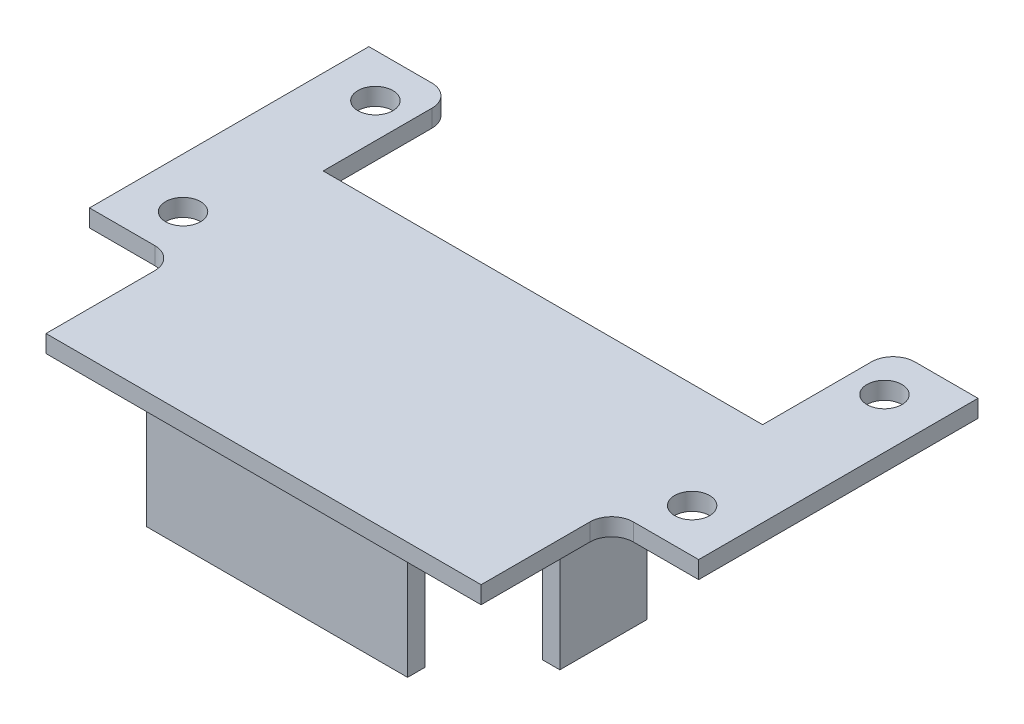
SolidWorks part; units mm, degrees
ref_plane "Front Plane" through (0, 0, 0) normal (0, 0, 1) x (1, 0, 0)
ref_plane "Top Plane" through (0, 0, 0) normal (0, 1, 0) x (1, 0, 0)
ref_plane "Right Plane" through (0, 0, 0) normal (1, 0, 0) x (0, 0, -1)
sketch "Sketch1" plane through (0, 0, 0) normal (0, 1, 0) x (1, 0, 0)
  line L0 (0, 0) -> (0, 20.3835) construction
  line L1 (44.45, -20.3835) -> (-44.45, -20.3835)
  line L2 (44.45, -20.3835) -> (44.45, 20.3835)
  line L3 (44.45, 20.3835) -> (-44.45, 20.3835) construction
  line L4 (-44.45, -20.3835) -> (-44.45, 20.3835)
  line L5 (44.45, -20.3835) -> (-44.45, 20.3835) construction
  line L6 (44.45, 20.3835) -> (-44.45, -20.3835) construction
  line L7 (0, 0) -> (44.45, 0) construction
  line L13 (-32.0675, 17.2085) -> (-32.0675, 1.3335)
  line L14 (-44.45, 20.3835) -> (-35.2425, 20.3835)
  line L15 (-32.0675, 1.3335) -> (32.0675, 1.3335)
  line L16 (32.0675, 17.2085) -> (32.0675, 1.3335)
  line L17 (44.45, 20.3835) -> (35.2425, 20.3835)
  circle A0 centre (37.1475, -14.0335) radius 2.5527
  circle A2 centre (37.1475, 14.0335) radius 2.5527
  circle A3 centre (-37.1475, -14.0335) radius 2.5527
  circle A4 centre (-37.1475, 14.0335) radius 2.5527
  arc A7 (-32.0675, 17.2085) -> (-35.2425, 20.3835) centre (-35.2425, 17.2085) ccw
  arc A8 (32.0675, 17.2085) -> (35.2425, 20.3835) centre (35.2425, 17.2085) cw
  point P0 (0, 0)
  point P19 (0, 1.3335)
  point P22 (0, 20.3835)
  point P23 (-32.0675, 20.3835)
  point P24 (44.45, 0)
  point P30 (32.0675, 20.3835)
  dimension "D3" = 5.1054
  dimension "D6" = 28.067
  dimension "D7" = 5.1054
  dimension "D10" = 5.08
  dimension "D12" = 3.175
  dimension "D1" = 6.35
  dimension "D2" = 88.9
  dimension "D4" = 6.35
  dimension "D5" = 7.3025
  dimension "D8" = 7.3025
  dimension "D11" = 19.05
extrude "Boss-Extrude1" add sketch "Sketch1" along normal blind 2.54
sketch "Sketch7" plane through (0, 2.54, 0) normal (0, 1, 0) x (1, 0, 0)
  line L1 (-44.45, -20.3835) -> (44.45, -20.3835)
  line L2 (-44.45, -20.3835) -> (-44.45, -39.4335)
  line L3 (-44.45, -39.4335) -> (44.45, -39.4335)
  line L4 (44.45, -20.3835) -> (44.45, -39.4335)
  dimension "D1" = 19.05
extrude "Boss-Extrude2" add sketch "Sketch7" against normal up to surface (2.54 mm away) up to face at (0, 0, -7.9166)
sketch "Sketch6" plane through (0, 0, 0) normal (0, -1, 0) x (-1, 0, 0)
  line L0 (0, 1.3335) -> (0, -39.4335) construction
  line L5 (-32.0675, 1.3335) -> (32.0675, 1.3335) construction
  line L11 (-44.45, -39.4335) -> (44.45, -39.4335) construction
  line L26 (25.4, -33.655) -> (-25.4, -33.655) construction
  line L27 (25.4, -33.655) -> (25.4, -4.445) construction
  line L28 (25.4, -4.445) -> (-25.4, -4.445) construction
  line L29 (-25.4, -33.655) -> (-25.4, -4.445) construction
  line L30 (25.4, -33.655) -> (-25.4, -4.445) construction
  line L31 (25.4, -4.445) -> (-25.4, -33.655) construction
  line L32 (0, -19.05) -> (44.45, -19.05) construction
  line L33 (44.45, 20.3835) -> (44.45, -39.4335) construction
  line L34 (-19.05, -34.925) -> (-19.05, -37.465)
  line L35 (26.67, -34.925) -> (-26.67, -34.925) construction
  line L36 (26.67, -34.925) -> (26.67, -3.175) construction
  line L37 (26.67, -3.175) -> (-26.67, -3.175) construction
  line L38 (-26.67, -34.925) -> (-26.67, -3.175) construction
  line L39 (26.67, -34.925) -> (-26.67, -3.175) construction
  line L40 (26.67, -3.175) -> (-26.67, -34.925) construction
  line L41 (-19.05, -34.925) -> (19.05, -34.925)
  line L42 (0, -34.925) -> (0, -37.465) construction
  line L43 (-19.05, -37.465) -> (19.05, -37.465)
  line L44 (19.05, -34.925) -> (19.05, -37.465)
  line L45 (-19.05, -3.175) -> (-19.05, -0.635)
  line L46 (-19.05, -3.175) -> (19.05, -3.175)
  line L47 (0, -3.175) -> (0, -0.635) construction
  line L48 (-19.05, -0.635) -> (19.05, -0.635)
  line L49 (19.05, -3.175) -> (19.05, -0.635)
  line L50 (26.67, -25.4) -> (29.21, -25.4)
  line L51 (26.67, -19.05) -> (29.21, -19.05) construction
  line L52 (26.67, -25.4) -> (26.67, -12.7)
  line L53 (26.67, -12.7) -> (29.21, -12.7)
  line L54 (29.21, -25.4) -> (29.21, -12.7)
  line L55 (-26.67, -25.4) -> (-26.67, -12.7)
  line L56 (-26.67, -12.7) -> (-29.21, -12.7)
  line L57 (-29.21, -25.4) -> (-29.21, -12.7)
  line L58 (-26.67, -25.4) -> (-29.21, -25.4)
  point P14 (0, -19.05)
  point P29 (19.05, -1.905)
  point P30 (-19.05, -1.905)
  dimension "D1" = 29.21
  dimension "D2" = 50.8
  dimension "D3" = 1.27
  dimension "D4" = 1.27
  dimension "D5" = 19.05
  dimension "D6" = 2.54
  dimension "D7" = 19.05
  dimension "D8" = 2.54
  dimension "D9" = 2.54
  dimension "D10" = 6.35
extrude "Boss-Extrude3" add sketch "Sketch6" along normal blind 16.51
sketch "Sketch8" plane through (0, 0, 0) normal (0, -1, 0) x (1, 0, 0)
  line L0 (0, 39.4335) -> (0, -1.3335) construction
  line L1 (-44.45, 39.4335) -> (-31.75, 39.4335)
  line L2 (-44.45, 39.4335) -> (-44.45, 20.3835)
  line L3 (-44.45, 20.3835) -> (-34.925, 20.3835)
  line L4 (-31.75, 39.4335) -> (-31.75, 23.5585)
  line L5 (44.45, 39.4335) -> (-44.45, 39.4335) construction
  line L6 (32.0675, -1.3335) -> (-32.0675, -1.3335) construction
  line L7 (44.45, 20.3835) -> (34.925, 20.3835)
  line L8 (31.75, 39.4335) -> (31.75, 23.5585)
  line L9 (44.45, 39.4335) -> (31.75, 39.4335)
  line L10 (44.45, 39.4335) -> (44.45, 20.3835)
  arc A0 (-34.925, 20.3835) -> (-31.75, 23.5585) centre (-34.925, 23.5585) ccw
  arc A1 (34.925, 20.3835) -> (31.75, 23.5585) centre (34.925, 23.5585) cw
  point P13 (-31.75, 20.3835)
  dimension "D3" = 3.175
  dimension "D1" = 12.7
  dimension "D2" = 19.05
extrude "Cut-Extrude1" cut sketch "Sketch8" against normal through all
